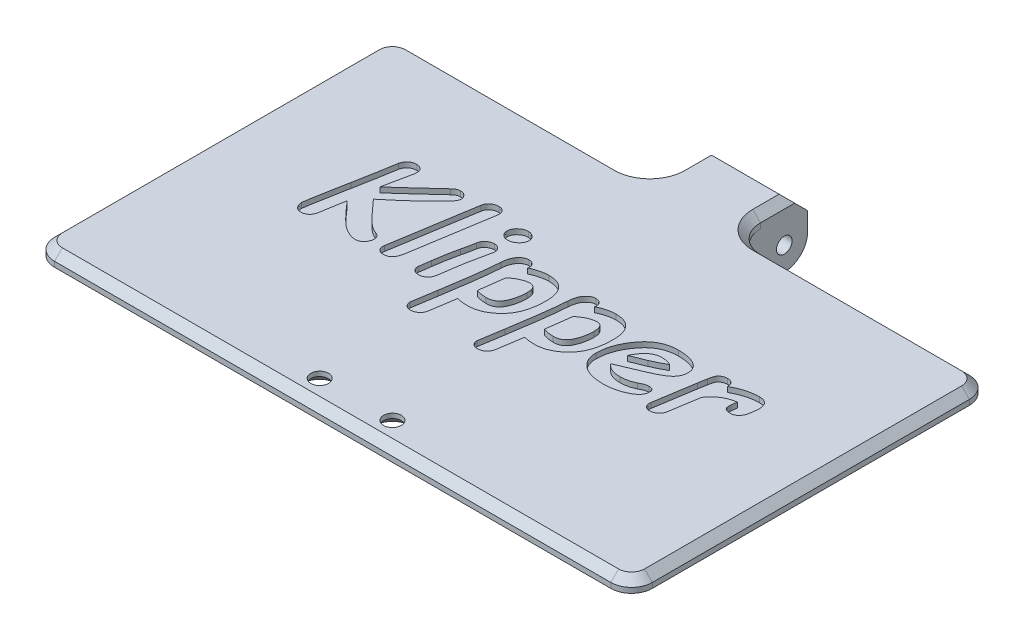
SolidWorks part; units mm, degrees
ref_plane "前视基准面" through (0, 0, 0) normal (0, 0, 1) x (1, 0, 0)
ref_plane "上视基准面" through (0, 0, 0) normal (0, 1, 0) x (1, 0, 0)
ref_plane "右视基准面" through (0, 0, 0) normal (1, 0, 0) x (0, 0, -1)
sketch "草图1" plane through (0, 0, 0) normal (0, 1, 0) x (1, 0, 0)
  line L1 (-57.5, 34.5) -> (57.5, 34.5)
  line L2 (-57.5, 34.5) -> (-57.5, -34.5)
  line L3 (-57.5, -34.5) -> (57.5, -34.5)
  line L4 (57.5, 34.5) -> (57.5, -34.5)
  line L5 (-57.5, 34.5) -> (57.5, -34.5) construction
  line L6 (-57.5, -34.5) -> (57.5, 34.5) construction
  point P0 (0, 0)
  dimension "D1" = 69
  dimension "D2" = 115
extrude "凸台-拉伸1" add sketch "草图1" along normal blind 2.5
sketch "草图2" plane through (0, 2.5, 0) normal (0, 1, 0) x (1, 0, 0)
  line L0 (0, 0) -> (0, 66.4249) construction
  line L1 (57.5, 34.5) -> (-57.5, 34.5) construction
  line L2 (-8, 44.38) -> (8, 44.38)
  line L3 (-8, 44.38) -> (-8, 34.5)
  line L4 (-8, 34.5) -> (8, 34.5)
  line L5 (8, 44.38) -> (8, 34.5)
  line L6 (-8, 44.38) -> (8, 34.5) construction
  line L7 (-8, 34.5) -> (8, 44.38) construction
  point P1 (0, 39.44)
  dimension "D1" = 9.88
  dimension "D2" = 16
extrude "凸台-拉伸2" add sketch "草图2" against normal up to surface (2.5 mm away) up to face at (0, 0, 0)
sketch "草图3" plane through (0, 0, 0) normal (1, 0, 0) x (0, 0, -1)
  line L0 (44.38, 0) -> (34.5, 0) construction
  line L1 (34.5, 2.5) -> (34.5, 0) construction
  circle A0 centre (44.38, -5) radius 1.5
  circle A1 centre (44.38, -5) radius 4.5
  dimension "D1" = 3
  dimension "D2" = 5
  dimension "D4" = 9.88
  dimension "D3" = 3
extrude "凸台-拉伸3" add sketch "草图3" along normal blind 8 and the other way blind 8 separate body
sketch "草图4" plane through (8, 0, 0) normal (1, 0, 0) x (0, 0, -1)
  line L0 (39.88, -5) -> (39.88, 2.5)
  line L1 (34.5, 2.5) -> (44.38, 2.5) construction
  line L2 (39.88, 2.5) -> (44.38, 2.5)
  line L3 (44.38, 2.5) -> (48.88, 2.5)
  line L4 (48.88, 2.5) -> (48.88, -5)
  line L5 (39.88, -5) -> (42.88, -5)
  line L7 (45.88, -5) -> (48.88, -5)
  circle A0 centre (44.38, -5) radius 4.5 construction
  arc A1 (45.88, -5) -> (42.88, -5) centre (44.38, -5) ccw
extrude "凸台-拉伸4" add sketch "草图4" against normal up to surface (16 mm away) up to face at (-8, 1.25, -39.44)
fillet "圆角1" radius 4 4 edges at (-57.5, 1.25, -34.5) (-57.5, 1.25, 34.5) (57.5, 1.25, 34.5) (57.5, 1.25, -34.5)
fillet "圆角2" radius 5.3 2 edges at (-8, 1.25, -34.5) (8, 1.25, -34.5)
chamfer "倒角3" distance 4 angle 45 1 edges at (0, 2.5, -48.88)
chamfer "倒角4" distance 5 angle 45 1 edges at (0, 0, -39.88)
sketch "草图5" plane through (0, 0, 0) normal (0, 0, 1) x (1, 0, 0)
  line L0 (-53.5, 0) -> (53.5, 0) construction
  line L1 (-8, 0) -> (-14.5322, 0)
  line L2 (-8, 0) -> (-8, -9.476)
  line L3 (-8, -9.476) -> (-14.5322, -9.476)
  line L4 (-14.5322, 0) -> (-14.5322, -9.476)
  line L6 (8, 0) -> (14.588, 0)
  line L7 (8, 0) -> (8, -9.476)
  line L8 (8, -9.476) -> (14.588, -9.476)
  line L9 (14.588, 0) -> (14.588, -9.476)
extrude "切除-拉伸1" cut sketch "草图5" against normal up to next
chamfer "倒角5" distance 1.5 angle 45 13 edges at (8, 2.5, -42.34) (9.5523, 2.5, -36.0523) (33.4, 2.5, -34.5) (56.3284, 2.5, -33.3284) (-8, 2.5, -42.34) (57.5, 2.5, 0) (-9.5523, 2.5, -36.0523) (56.3284, 2.5, 33.3284) (-33.4, 2.5, -34.5) (0, 2.5, 34.5) (-56.3284, 2.5, -33.3284) (-56.3284, 2.5, 33.3284) (-57.5, 2.5, 0)
sketch "草图6" plane through (0, 2.5, 0) normal (0, 1, 0) x (1, 0, 0)
  line L0 (-56, -3.0078) -> (56, -3.0078) construction
  line L1 (-56, 30.5) -> (-56, -30.5) construction
  line L2 (56, -30.5) -> (56, 30.5) construction
  text T0 "Klipper" font "Comic Sans MS" height 18
extrude "切除-拉伸2" cut sketch "草图6" against normal blind 1
sketch "草图7" plane through (0, 0, 0) normal (0, -1, 0) x (1, 0, 0)
  line L0 (-57.5, 30) -> (57.5, 30) construction
  line L1 (-57.5, -30.5) -> (-57.5, 30.5) construction
  line L2 (57.5, 30.5) -> (57.5, -30.5) construction
  line L3 (0, 30) -> (0, 17.406) construction
  line L4 (-53.5, 34.5) -> (53.5, 34.5) construction
  circle A0 centre (-7, 30) radius 1.5
  circle A2 centre (7, 30) radius 1.5
  point P10 (0, 30)
  dimension "D2" = 3
  dimension "D1" = 7
  dimension "D3" = 4.5
extrude "切除-拉伸3" cut sketch "草图7" against normal blind 10
hole_wizard "打孔尺寸(%根据十字)槽半沉头木螺钉的类型1" positions "草图8" profile "草图9" countersink size "M3" standard "GB" end condition through all
sketch "草图8" plane through (0, 0, 0) normal (0, -1, 0) x (-1, 0, 0)
  point P0 (-7, -30)
  point P3 (7, -30)
sketch "草图9" plane through (7, 0, 30) normal (1, 0, 0) x (0, 0, -1)
  line L0 (0, 0) -> (0, 2.5)
  line L1 (0, 2.5) -> (1.7, 2.5)
  line L2 (1.7, 2.5) -> (1.7, 1.6)
  line L3 (1.7, 1.6) -> (3.3, 0)
  line L5 (3.3, 0) -> (0, 0)
  line L6 (-1.7, 1.6) -> (-3.3, 0) construction
  line L11 (0, -6.35) -> (0, 107.95) construction
  dimension "通孔孔直径" = 3.4
  dimension "通孔孔深度" = 2.5
  dimension "近端锥形沉头孔直径" = 6.6
  dimension "近端锥形沉头孔角度" = 90
